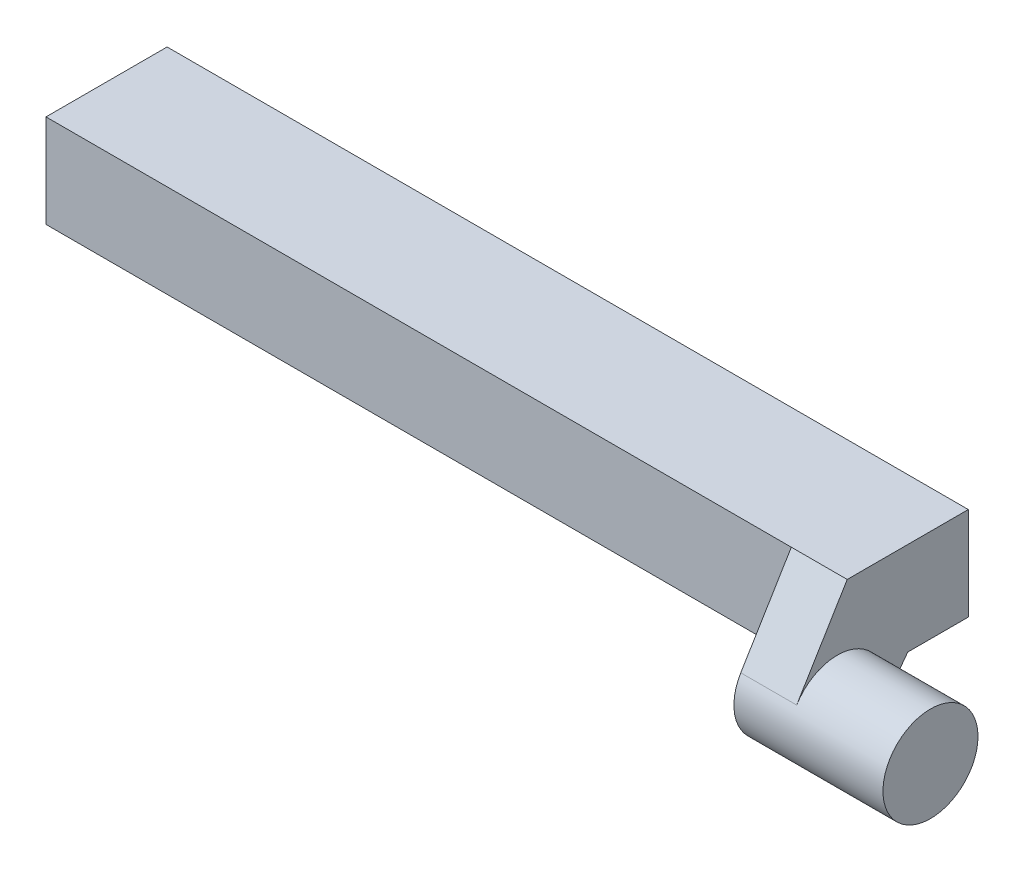
SolidWorks part; units mm, degrees
ref_plane "Front Plane" through (0, 0, 0) normal (0, 0, 1) x (1, 0, 0)
ref_plane "Top Plane" through (0, 0, 0) normal (0, 1, 0) x (1, 0, 0)
ref_plane "Right Plane" through (0, 0, 0) normal (1, 0, 0) x (0, 0, -1)
sketch "Sketch2" plane through (0, 0, 0) normal (1, 0, 0) x (0, 0, -1)
  line L1 (-2.25, -2.25) -> (2.25, -2.25)
  line L2 (-2.25, -2.25) -> (-2.25, 2.25)
  line L3 (-2.25, 2.25) -> (2.25, 2.25)
  line L4 (2.25, -2.25) -> (2.25, 2.25)
  line L5 (-2.25, -2.25) -> (2.25, 2.25) construction
  line L6 (-2.25, 2.25) -> (2.25, -2.25) construction
  line L7 (3.25, -2.5) -> (-3.25, -2.5)
  line L8 (3.25, -2.5) -> (3.25, 2.5)
  line L9 (3.25, 2.5) -> (-3.25, 2.5)
  line L10 (-3.25, -2.5) -> (-3.25, 2.5)
  line L11 (3.25, -2.5) -> (-3.25, 2.5) construction
  line L12 (3.25, 2.5) -> (-3.25, -2.5) construction
  point P0 (0, 0)
  point P5 (0, 0)
  dimension "D1" = 4.5
  dimension "D2" = 4.5
  dimension "D3" = 6.5
  dimension "D4" = 5
extrude "Boss-Extrude1" add sketch "Sketch2" along normal blind 10
extrude "Boss-Extrude2" add sketch "Sketch2<2>" along normal blind 30 from surface contours L1 L4 L3 L2 | L10 L7 L8 L9 L4 L1 L2 L3 region at (0, 0, 0) region at (0, -2.418, 0) starting at face at (10, 0, 0)
sketch "Sketch2<2>" plane through (0, 0, 0) normal (1, 0, 0) x (0, 0, -1) same geometry as "Sketch2"
sketch "Sketch5" plane through (40, 0, 0) normal (1, 0, 0) x (0, 0, -1)
  line L0 (-0.02, -0.4959) -> (-4.75, -0.4959) construction
  line L5 (-5.9623, -1.983) -> (-3.25, 2.5)
  line L6 (-3.25, 2.5) -> (3.25, 2.5)
  line L7 (3.25, 2.5) -> (3.25, -2.5)
  line L8 (3.25, -2.5) -> (0, -2.5)
  line L9 (-3.25, -2.5) -> (3.25, -2.5) construction
  line L10 (0, -2.5) -> (-1.7367, -4.8278)
  arc A1 (-5.9623, -1.983) -> (-1.7367, -4.8278) centre (-3.7806, -3.303) ccw
  dimension "D2" = 2.55
  dimension "D1" = 4.73
  dimension "D3" = 5
extrude "Boss-Extrude3" add sketch "Sketch5" along normal blind 3
sketch "Sketch6" plane through (43, 0, 0) normal (1, 0, 0) x (0, 0, -1)
  circle A1 centre (-3.7806, -3.303) radius 2.55
  dimension "D1" = 5.1
extrude "Boss-Extrude4" add sketch "Sketch6" along normal blind 5
